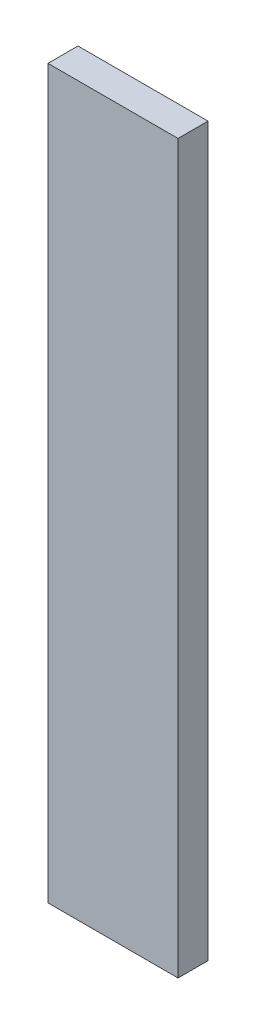
SolidWorks part; units mm, degrees
ref_plane "Front Plane" through (0, 0, 0) normal (0, 0, 1) x (1, 0, 0)
ref_plane "Top Plane" through (0, 0, 0) normal (0, 1, 0) x (1, 0, 0)
ref_plane "Right Plane" through (0, 0, 0) normal (1, 0, 0) x (0, 0, -1)
sketch "Sketch1" plane through (0, 0, 0) normal (0, 1, 0) x (1, 0, 0)
  line L1 (-97.5, 22.5) -> (97.5, 22.5)
  line L2 (-97.5, 22.5) -> (-97.5, -22.5)
  line L3 (-97.5, -22.5) -> (97.5, -22.5)
  line L4 (97.5, 22.5) -> (97.5, -22.5)
  line L5 (-97.5, 22.5) -> (97.5, -22.5) construction
  line L6 (-97.5, -22.5) -> (97.5, 22.5) construction
  point P0 (0, 0)
  dimension "D1" = 45
  dimension "D2" = 195
extrude "Shape" add sketch "Sketch1" along normal blind 1090
